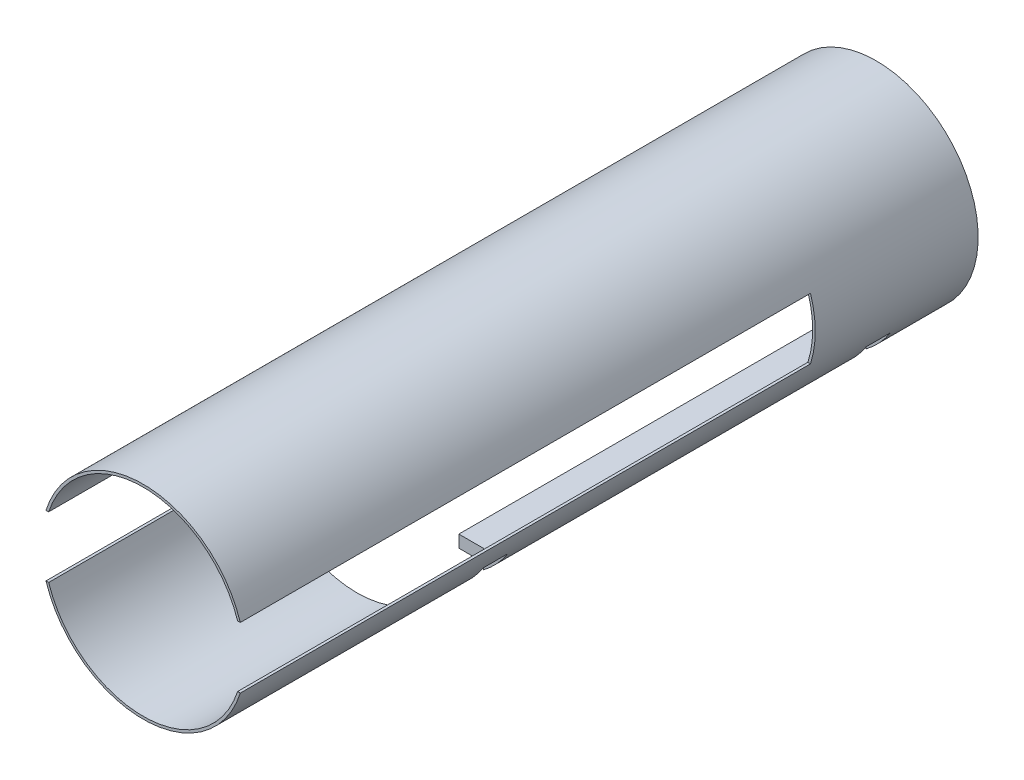
SolidWorks part; units mm, degrees
ref_plane "Front Plane" through (0, 0, 0) normal (0, 0, 1) x (1, 0, 0)
ref_plane "Top Plane" through (0, 0, 0) normal (0, 1, 0) x (1, 0, 0)
ref_plane "Right Plane" through (0, 0, 0) normal (1, 0, 0) x (0, 0, -1)
sketch "Sketch1" plane through (0, 0, 0) normal (0, 0, 1) x (1, 0, 0)
  line L1 (-88.9, -19.05) -> (88.9, -19.05)
  line L2 (-88.9, -19.05) -> (-88.9, 19.05) construction
  line L3 (-88.9, 19.05) -> (88.9, 19.05)
  line L4 (88.9, -19.05) -> (88.9, 19.05) construction
  line L5 (-88.9, -19.05) -> (88.9, 19.05) construction
  line L6 (-88.9, 19.05) -> (88.9, -19.05) construction
  circle A0 centre (0, 0) radius 63.5
  circle A1 centre (0, 0) radius 61.9125
  dimension "D1" = 127
  dimension "D4" = 1.5875
  dimension "D2" = 38.1
  dimension "D3" = 177.8
extrude "Boss-Extrude1" add sketch "Sketch1" along normal mid plane 355.6 contours A1 L3 A0 | A1 L1 A0 region at (-59.742, -20.3405, 0) region at (0, 62.2095, 0)
sketch "Sketch2" plane through (0, 0, -177.8) normal (0, 0, -1) x (-1, 0, 0)
  circle A0 centre (0, 0) radius 63.5 construction
  circle A1 centre (0, 0) radius 61.9125 construction
  circle A2 centre (0, 0) radius 63.5
  circle A3 centre (0, 0) radius 61.9125
extrude "Boss-Extrude2" add sketch "Sketch2" along normal blind 101.6
ref_plane "Plane1" through (0, 0, -273.05) normal (0, 0, -1) x (-1, 0, 0)
sketch "Sketch3" plane through (0, 0, -273.05) normal (0, 0, -1) x (-1, 0, 0)
  line L0 (0, 0) -> (0, 44.45)
  line L1 (0, 0) -> (44.45, 0)
  line L2 (0, 0) -> (0, -44.45)
  line L3 (0, 0) -> (-44.45, 0)
  circle A0 centre (0, 0) radius 61.9125
  circle A1 centre (0, 0) radius 31.75
  point P11 (0, 0)
  dimension "D1" = 63.5
  dimension "D2" = 123.825
  dimension "D3" = 44.45
  dimension "D4" = 4
extrude "Boss-Extrude3" add sketch "Sketch3" against normal blind 12.7 contours A0 A1 region at (60.1614, 0, -273.05)
hole_wizard "1/4 (0.25) Diameter Hole1" positions "3DSketch2" profile "Sketch5" hole size "1/4" standard "ANSI Inch"
sketch3d "3DSketch2"
  point P0 (0, 44.45, -273.05)
  point P3 (-44.45, 0, -273.05)
  point P6 (0, -44.45, -273.05)
  point P9 (44.45, 0, -273.05)
sketch "Sketch5" plane through (0, 44.45, -273.05) normal (1, 0, 0) x (0, 1, 0)
  line L0 (0, 0) -> (0, 44.958)
  line L1 (0, 44.958) -> (3.175, 44.958)
  line L2 (3.175, 44.958) -> (3.175, 0)
  line L5 (3.175, 0) -> (0, 0)
  line L10 (0, 44.958) -> (-3.175, 44.958) construction
  line L11 (0, -6.35) -> (0, 107.95) construction
  dimension "Hole Dia." = 6.35
  dimension "Hole Depth" = 44.958
  dimension "Drill Angle" = 180
sketch "Sketch6" plane through (0, -19.05, 0) normal (0, 1, 0) x (1, 0, 0)
  line L0 (0, -69.85) -> (0, 69.85) construction
  line L1 (38.1, 234.95) -> (53.34, 234.95)
  line L2 (38.1, 234.95) -> (38.1, 219.71)
  line L3 (38.1, 219.71) -> (53.34, 219.71)
  line L4 (-38.1, -19.05) -> (-38.1, -44.45)
  line L5 (38.1, 260.35) -> (-38.1, 260.35)
  line L6 (38.1, 234.95) -> (38.1, 260.35)
  line L7 (-38.1, -44.45) -> (38.1, -44.45)
  line L8 (-38.1, -19.05) -> (-38.1, -44.45)
  line L9 (38.1, 260.35) -> (-38.1, 260.35)
  line L10 (38.1, 234.95) -> (38.1, 260.35)
  line L11 (-38.1, -44.45) -> (38.1, -44.45)
  line L12 (53.34, 234.95) -> (53.34, 219.71)
  line L13 (38.1, -3.81) -> (53.34, -3.81)
  line L14 (38.1, -3.81) -> (38.1, -19.05)
  line L15 (38.1, -19.05) -> (53.34, -19.05)
  line L16 (53.34, -3.81) -> (53.34, -19.05)
  line L17 (-38.1, -19.05) -> (-53.34, -19.05)
  line L18 (-53.34, -3.81) -> (-53.34, -19.05)
  line L19 (-38.1, -3.81) -> (-53.34, -3.81)
  line L20 (-38.1, 219.71) -> (-53.34, 219.71)
  line L21 (-53.34, 234.95) -> (-53.34, 219.71)
  line L22 (-38.1, 234.95) -> (-53.34, 234.95)
  line L87 (-38.1, 260.35) -> (-38.1, 234.95)
  line L88 (-38.1, 260.35) -> (-38.1, 234.95)
  line L89 (53.34, 234.95) -> (38.1, 234.95)
  line L90 (53.34, 234.95) -> (38.1, 234.95)
  line L91 (53.34, 219.71) -> (53.34, 234.95)
  line L92 (53.34, 219.71) -> (53.34, 234.95)
  line L93 (38.1, 219.71) -> (53.34, 219.71)
  line L94 (38.1, 219.71) -> (53.34, 219.71)
  line L95 (38.1, -3.81) -> (38.1, 219.71)
  line L96 (38.1, -3.81) -> (38.1, 219.71)
  line L97 (53.34, -3.81) -> (38.1, -3.81)
  line L98 (53.34, -3.81) -> (38.1, -3.81)
  line L99 (53.34, -19.05) -> (53.34, -3.81)
  line L100 (53.34, -19.05) -> (53.34, -3.81)
  line L101 (38.1, -19.05) -> (53.34, -19.05)
  line L102 (38.1, -19.05) -> (53.34, -19.05)
  line L103 (38.1, -44.45) -> (38.1, -19.05)
  line L104 (38.1, -44.45) -> (38.1, -19.05)
  line L105 (-53.34, -19.05) -> (-38.1, -19.05)
  line L106 (-53.34, -19.05) -> (-38.1, -19.05)
  line L107 (-53.34, -3.81) -> (-53.34, -19.05)
  line L108 (-53.34, -3.81) -> (-53.34, -19.05)
  line L109 (-38.1, -3.81) -> (-53.34, -3.81)
  line L110 (-38.1, -3.81) -> (-53.34, -3.81)
  line L111 (-38.1, 219.71) -> (-38.1, -3.81)
  line L112 (-38.1, 219.71) -> (-38.1, -3.81)
  line L113 (-53.34, 219.71) -> (-38.1, 219.71)
  line L114 (-53.34, 219.71) -> (-38.1, 219.71)
  line L115 (-53.34, 234.95) -> (-53.34, 219.71)
  line L116 (-53.34, 234.95) -> (-53.34, 219.71)
  line L117 (-38.1, 234.95) -> (-53.34, 234.95)
  line L118 (-38.1, 234.95) -> (-53.34, 234.95)
  dimension "D2" = 15.24
  dimension "D3" = 15.24
  dimension "D4" = 15.24
  dimension "D5" = 15.24
  dimension "D1" = 0
extrude "Cut-Extrude1" cut sketch "Sketch6" against normal through all contours L8 L11 L10 L2 L9 | L8 L19 L18 L17 | L8 L22 L21 L20 | L12 L1 L2 L3 | L16 L13 L10 L15 region at (45.72, -19.05, -227.33) region at (-0.8965, -19.05, -107.95) region at (45.72, -19.05, 11.43)
sketch "Sketch7" plane through (0, 0, -260.35) normal (0, 0, 1) x (1, 0, 0)
  line L0 (-53.34, -23.8125) -> (-57.15, -23.8125)
  line L1 (-53.34, -31.4325) -> (-38.1, -31.4325)
  line L2 (38.1, -48.8011) -> (38.1, -50.8)
  line L3 (53.34, -34.4542) -> (53.34, -31.4325)
  line L4 (38.1, -48.8011) -> (38.1, -50.8)
  line L5 (53.34, -34.4542) -> (53.34, -31.4325)
  line L6 (-53.34, -31.4325) -> (-53.34, -34.4542)
  line L7 (-38.1, -50.8) -> (-38.1, -48.8011)
  line L8 (-53.34, -31.4325) -> (-53.34, -34.4542)
  line L10 (-53.34, -31.4325) -> (-53.34, -23.8125)
  line L11 (-53.34, -23.8125) -> (-38.1, -23.8125)
  line L12 (-38.1, -31.4325) -> (-38.1, -23.8125)
  line L13 (53.34, -31.4325) -> (38.1, -31.4325)
  line L14 (53.34, -31.4325) -> (53.34, -23.8125)
  line L15 (53.34, -23.8125) -> (38.1, -23.8125)
  line L16 (38.1, -31.4325) -> (38.1, -23.8125)
  line L17 (53.34, -23.8125) -> (57.15, -23.8125)
  line L20 (-38.1, -50.8) -> (-38.1, -48.8011)
  arc A0 (-58.9089, -19.05) -> (58.9089, -19.05) centre (0, 0) ccw construction
  arc A2 (38.1, -50.8) -> (53.34, -34.4542) centre (0, 0) ccw
  arc A3 (38.1, -48.8011) -> (53.34, -31.4325) centre (0, 0) ccw
  arc A4 (38.1, -50.8) -> (53.34, -34.4542) centre (0, 0) ccw
  arc A5 (38.1, -48.8011) -> (53.34, -31.4325) centre (0, 0) ccw
  arc A6 (-53.34, -31.4325) -> (-38.1, -48.8011) centre (0, 0) ccw
  arc A7 (-53.34, -34.4542) -> (-38.1, -50.8) centre (0, 0) ccw
  arc A8 (-53.34, -31.4325) -> (-38.1, -48.8011) centre (0, 0) ccw
  arc A9 (-53.34, -34.4542) -> (-38.1, -50.8) centre (0, 0) ccw
  arc M12 (38.1, -48.8011) -> (-38.1, -48.8011) centre (0, 0) ccw
  dimension "D3" = 15.24
  dimension "D4" = 7.62
  dimension "D5" = 15.24
  dimension "D1" = 0
  dimension "D2" = 0
extrude "Boss-Extrude6" add sketch "Sketch7" along normal up to surface (279.4 mm away) contours L17 L14 M12 | L16 L13 L14 L15 | L10 L0 M12 | L1 L12 L11 L10 region at (-54.6473, -26.4229, -260.35) region at (-45.72, -27.6225, -260.35) region at (54.6473, -26.4229, -260.35) region at (45.72, -27.6225, -260.35) up to face at (-46.1056, -41.7202, 19.05)
sketch "Sketch8" plane through (0, -31.4325, 0) normal (0, -1, 0) x (1, 0, 0)
  line L0 (-53.34, 3.81) -> (-53.34, 19.05) construction
  line L1 (-53.34, 19.05) -> (-38.1, 19.05) construction
  line L2 (-53.34, -219.71) -> (-38.1, -219.71) construction
  line L3 (-53.34, -234.95) -> (-53.34, -219.71) construction
  line L4 (0, -69.85) -> (0, 69.85) construction
  circle A0 centre (-45.72, 11.3526) radius 2.54
  circle A1 centre (-45.72, -227.33) radius 2.54
  circle A2 centre (45.72, 11.3526) radius 2.54
  circle A3 centre (45.72, -227.33) radius 2.54
  dimension "D1" = 5.08
  dimension "D4" = 5.08
  dimension "D2" = 7.62
  dimension "D3" = 7.6974
  dimension "D5" = 7.62
  dimension "D6" = 7.62
extrude "Cut-Extrude2" cut sketch "Sketch8" against normal blind 5.08
